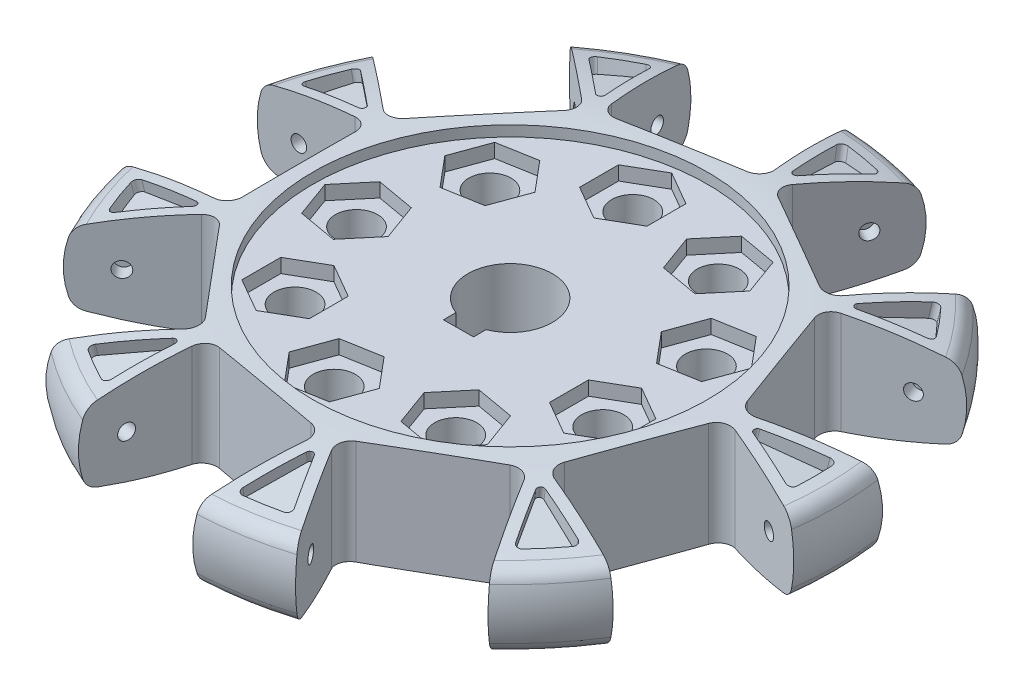
SolidWorks part; units mm, degrees
ref_plane "前视基准面" through (0, 0, 0) normal (0, 0, 1) x (1, 0, 0)
ref_plane "上视基准面" through (0, 0, 0) normal (0, 1, 0) x (1, 0, 0)
ref_plane "右视基准面" through (0, 0, 0) normal (1, 0, 0) x (0, 0, -1)
sketch "草图1" plane through (0, 0, 0) normal (0, 0, 1) x (1, 0, 0)
  line L0 (-6, 6.0015) -> (-6, -6.0015)
  line L1 (-6, -6.0015) -> (-28, -6.0015)
  line L2 (-28, -6.0015) -> (-28, -7.5)
  line L3 (0, 0) -> (-35.4086, 0) construction
  line L4 (-28, 6.0015) -> (-28, 7.5)
  line L5 (-6, 6.0015) -> (-28, 6.0015)
  line L6 (0, 18.3487) -> (0, -10.7173) construction
  arc A2 (-44.6978, -5.3531) -> (-46.4676, -3.6239) centre (-44.0685, -2.9388) cw
  arc A3 (-46.4734, 3.6245) -> (-44.7045, 5.3513) centre (-44.075, 2.9371) cw
  spline S0 degree 3 poles (-28, 7.5) (-33.6148, 7.5064) (-39.1867, 6.7902) (-44.7045, 5.3513) knots 0 0 0 0 0.927371 0.927371 0.927371 0.927371
  spline S1 degree 3 poles (-28, -7.5) (-33.6125, -7.5064) (-39.1822, -6.7908) (-44.6978, -5.3531) knots 0 0 0 0 0.926994 0.926994 0.926994 0.926994
  spline S2 degree 3 poles (-46.4734, 3.6245) (-46.8154, 2.4311) (-47.1565, -0.006) (-46.8116, -2.4193) (-46.4676, -3.6239) knots 0.139652 0.139652 0.139652 0.139652 0.501009 0.862386 0.862386 0.862386 0.862386
  point P10 (-6, 0)
  dimension "D6" = 2.495
  dimension "D7" = 46.985
  dimension "D8" = 16.7045
  dimension "D10" = 5.3513
  dimension "D11" = 5.3531
  dimension "D12" = 16.6978
  dimension "D1" = 22
  dimension "D2" = 6
  dimension "D3" = 15
  dimension "D4" = 12.003
  dimension "D5" = 0.149
  dimension "D9" = 16.075
  dimension "D13" = 16.0685
  dimension "D14" = 7.2483
  dimension "D15" = 18.4676
  dimension "D16" = 0.149
revolve "旋转1" add sketch "草图1" angle 360 about L6
ref_plane "基准面1" through (0, 11.0015, 0) normal (0, 1, 0) x (1, 0, 0)
sketch "草图3" plane through (0, 11.0015, 0) normal (0, 1, 0) x (1, 0, 0)
  line L0 (-24.6448, 0) -> (-53.3107, 0) construction
  line L1 (-46.4354, 10) -> (-32, 10)
  line L2 (-30, 8) -> (-30, -8)
  line L3 (-46.4354, -10) -> (-32, -10)
  arc A1 (-46.4354, 10) -> (-46.4354, -10) centre (0, 0) ccw
  arc A2 (-32, 10) -> (-30, 8) centre (-32, 8) cw
  arc A3 (-30, -8) -> (-32, -10) centre (-32, -8) cw
  point P9 (-30, 0)
  point P12 (-30, 10)
  point P15 (-30, -10)
  dimension "D1" = 47.5
  dimension "D4" = 2
  dimension "D2" = 10
  dimension "D3" = 30
extrude "切除-拉伸1" cut sketch "草图3" against normal through all
pattern_circular "阵列(圆周)1" count 9 over 360 about axis through (0, 18.3487, 0) along (0, 1, 0) of "切除-拉伸1" reverse direction yes
ref_plane "基准面2" through (-2.9125, 13.8818, 0) normal (-0.2053, 0.9787, 0) x (-0.9787, -0.2053, 0)
sketch "草图5" plane through (-2.9125, 13.8818, 0) normal (-0.2053, 0.9787, 0) x (-0.9787, -0.2053, 0)
  line L4 (39.6288, -11.5) -> (29.825, -11.5)
  line L5 (38.7047, -11.5) -> (30.858, -11.5)
  arc A0 (36.602, -17.4074) -> (37.6876, -17.136) centre (37.0428, -16.8636) ccw
  arc A1 (38.7047, -11.5) -> (39.3764, -12.3968) centre (38.7047, -12.2) cw
  arc A3 (30.858, -11.5) -> (30.5283, -12.4088) centre (30.858, -12.0142) ccw
  spline S2 degree 3 poles (2501.9854, -1707.644) (-2855.6213, 2237.0556) (2819.504, -2395.7864) (-2122.0091, 2061.8679) knots -51.47026 -51.47026 -51.47026 -51.47026 52.584612 52.584612 52.584612 52.584612 only from (29.7529, -11.7596) to (37.3176, -17.9863)
  spline S3 degree 3 poles (-43.7224, 2948.346) (-409.4462, -78.3451) (2.2851, -116.7057) (75.0032, 87.3719) (-265.839, 330.4781) (-1916.2011, -2241.8859) knots -46.5867 -46.5867 -46.5867 -46.5867 0.5 0.5 47.70093 47.70093 47.70093 47.70093 only from (37.3176, -17.9863) to (39.6288, -11.5)
  spline S4 degree 3 poles (30.5283, -12.4088) (32.5382, -14.0884) (34.5661, -15.7573) (36.602, -17.4074) knots 0.103337 0.103337 0.103337 0.103337 0.906002 0.906002 0.906002 0.906002
  spline S5 degree 3 poles (37.6876, -17.136) (38.014, -16.3635) (38.6224, -14.7997) (39.1405, -13.2022) (39.3764, -12.3968) knots 0.134678 0.134678 0.134678 0.134678 0.5 0.864973 0.864973 0.864973 0.864973
  point P9 (38.5931, -14.8101)
  dimension "D2" = 0.7
  dimension "D3" = 8.2249
  dimension "D4" = 0.5142
  dimension "D1" = 1.5
extrude "切除-拉伸3" cut sketch "草图5" against normal blind 2
ref_plane "基准面3" through (0, 0, 0) normal (0, 1, 0) x (1, 0, 0)
mirror "镜向1" about plane through (0, 0, 0) normal (0, 1, 0) of "切除-拉伸3"
pattern_circular "阵列(圆周)2" count 9 every 40 about axis through (0, 18.3487, 0) along (0, 1, 0) of "切除-拉伸3", "镜向1" reverse direction yes
sketch "草图6" plane through (0, 6.0015, 0) normal (0, 1, 0) x (1, 0, 0)
  line L0 (0, 0) -> (38.4767, -13.7093) construction
  circle A0 centre (20.4081, -7.2715) radius 3
  point P6 (0, 0)
  point P7 (0, 0)
  dimension "D2" = 6
  dimension "D1" = 21.6648
extrude "切除-拉伸4" cut sketch "草图6" against normal through all
sketch "草图7" plane through (0, 6.0015, 0) normal (0, 1, 0) x (1, 0, 0)
  line L1 (15.6233, -10.034) -> (20.4081, -12.7965)
  line L2 (20.4081, -12.7965) -> (25.1929, -10.034)
  line L3 (25.1929, -10.034) -> (25.1929, -4.509)
  line L4 (25.1929, -4.509) -> (20.4081, -1.7465)
  line L5 (20.4081, -1.7465) -> (15.6233, -4.509)
  line L6 (15.6233, -4.509) -> (15.6233, -10.034)
  circle A0 centre (20.4081, -7.2715) radius 4.7848 construction
  dimension "D1" = 11.05
extrude "切除-拉伸5" cut sketch "草图7" against normal blind 2
pattern_circular "阵列(圆周)3" count 9 every 40 about axis through (0, 18.3487, 0) along (0, 1, 0) of "切除-拉伸4", "切除-拉伸5"
sketch "草图9" plane through (9.8481, 0, 1.7365) normal (-0.9848, 0, -0.1736) x (-0.1736, 0, 0.9848)
  circle A0 centre (40, 0) radius 1.1
  dimension "D2" = 2.2
  dimension "D1" = 40
extrude "切除-拉伸7" cut sketch "草图9" against normal blind 2
ref_plane "基准面4" through (0, 0, 0) normal (-0.9848, 0, -0.1736) x (-0.1736, 0, 0.9848)
mirror "镜向5" about plane through (0, 0, 0) normal (-0.9848, 0, -0.1736) of "切除-拉伸7"
pattern_circular "阵列(圆周)4" count 9 every 40 about axis through (0, 18.3487, 0) along (0, 1, 0) of "镜向5", "切除-拉伸7"
sketch "草图10" plane through (0, -6.0015, 0) normal (0, -1, 0) x (1, 0, 0)
  line L2 (2.1713, 5.5933) -> (2.1866, 7.3769) construction
  line L3 (2.1866, 7.3769) -> (-2.0596, 7.4133) construction
  line L4 (-2.0596, 7.4133) -> (-2.0749, 5.6298) construction
  line L5 (2.1713, 5.5933) -> (2.1866, 7.3769)
  line L6 (2.1866, 7.3769) -> (-2.0596, 7.4133)
  line L7 (-2.0596, 7.4133) -> (-2.0749, 5.6298)
  line L8 (2.1713, 5.5933) -> (-2.0749, 5.6298)
extrude "切除-拉伸8" cut sketch "草图10" against normal through all
